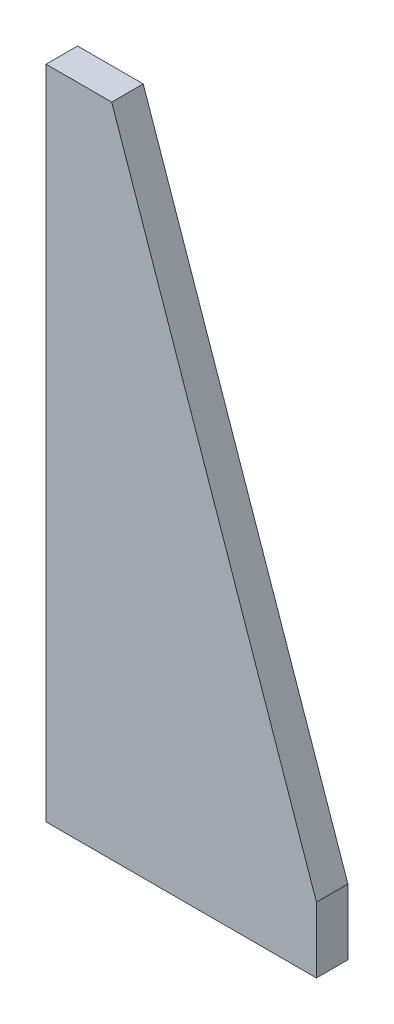
SolidWorks part; units mm, degrees
material "AISI 1020"
ref_plane "Plano frontal" through (0, 0, 0) normal (0, 0, 1) x (1, 0, 0)
ref_plane "Plano superior" through (0, 0, 0) normal (0, 1, 0) x (1, 0, 0)
ref_plane "Plano direito" through (0, 0, 0) normal (1, 0, 0) x (0, 0, -1)
sketch "Esboço1" plane through (0, 0, 0) normal (0, 0, 1) x (1, 0, 0)
  line L0 (0, 0) -> (41.2, 0)
  line L1 (41.2, 0) -> (41.2, 10)
  line L2 (41.2, 10) -> (10, 100)
  line L3 (10, 100) -> (0, 100)
  line L4 (0, 100) -> (0, 0)
  dimension "D1" = 41.2
  dimension "D2" = 10
  dimension "D3" = 10
  dimension "D4" = 100
base flange "Flange-base1" sketch "Esboço1" thickness 4.8 reverse thickness direction no parameters "D1"=5
sketch "Curva-Linhas1" [suppressed] plane through (0, 0, 0) normal (0, 1, 0) x (1, 0, 0)
sketch "Caixa delimitadora1" [suppressed] plane through (0, 0, 0) normal (0, 1, 0) x (1, 0, 0)
sheet metal parameters "Chapa metálica1" thickness 4.8 parameters "D1"=5
flat pattern "Padrão-Plano1" [suppressed]
sketch "Curva-Linhas2" plane through (0, 0, 0) normal (0, 1, 0) x (1, 0, 0)
sketch3d "Caixa delimitadora2" [suppressed]
  line L0 (-41.2, 100, 0) -> (-41.2, 0, 0) construction
  line L1 (0, 100, 0) -> (0, 0, 0) construction
  line L2 (-41.2, 100, 0) -> (0, 100, 0) construction
  line L3 (-41.2, 0, 0) -> (0, 0, 0) construction
